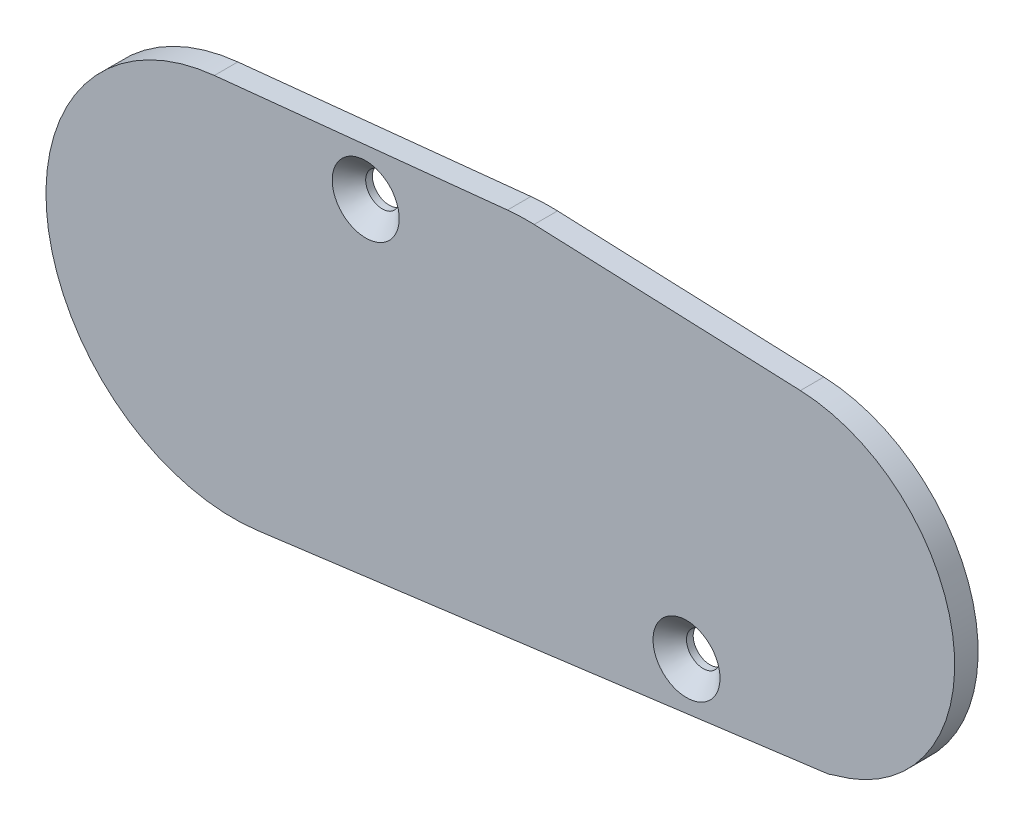
SolidWorks part; units mm, degrees
ref_plane "Front Plane" through (0, 0, 0) normal (0, 0, 1) x (1, 0, 0)
ref_plane "Top Plane" through (0, 0, 0) normal (0, 1, 0) x (1, 0, 0)
ref_plane "Right Plane" through (0, 0, 0) normal (1, 0, 0) x (0, 0, -1)
sketch "Sketch1" plane through (0, 0, 0) normal (0, 0, 1) x (1, 0, 0)
  line L0 (-43.969, -24.5) -> (-40.2721, -28.1969)
  line L2 (-40.2721, -28.1969) -> (-40.2721, -60)
  line L5 (63.3122, 76.6851) -> (41.4267, 78.9271)
  line L6 (39.439, 78.9888) -> (19.5552, 78.1913)
  line L7 (89.7279, -60) -> (89.7279, -34.5442)
  line L8 (77.7279, -22.5442) -> (52.2721, -22.5442)
  line L9 (40.2721, -34.5442) -> (40.2721, -60)
  line L10 (43.7868, -68.4853) -> (56.5147, -81.2132)
  line L11 (73.4853, -81.2132) -> (86.2132, -68.4853)
  line L12 (89.7279, -60) -> (89.7279, -34.5442)
  line L13 (-70.4772, -24.5) -> (-82.469, -24.5)
  line L14 (-84.469, -26.5) -> (-84.469, -49.0641)
  line L15 (-86.2132, -68.4853) -> (-73.4853, -81.2132)
  line L16 (-56.5147, -81.2132) -> (-43.7868, -68.4853)
  line L17 (-40.2721, -60) -> (-40.2721, -50)
  line L18 (-40.2721, -50) -> (-42.2721, -50)
  line L19 (-42.2721, -50) -> (-42.2721, -60)
  line L20 (-45.201, -67.0711) -> (-57.9289, -79.799)
  line L21 (-72.0711, -79.799) -> (-84.799, -67.0711)
  line L22 (-82.469, -51.1953) -> (-82.469, -26.5)
  line L23 (-82.469, -26.5) -> (-43.969, -26.5)
  line L24 (-43.969, -26.5) -> (-43.969, -24.5)
  line L25 (-43.969, -24.5) -> (-59.5228, -24.5)
  line L26 (-70.4772, -24.5) -> (-82.469, -24.5)
  line L27 (-84.469, -26.5) -> (-84.469, -49.0641)
  line L28 (-86.2132, -68.4853) -> (-73.4853, -81.2132)
  line L29 (-56.5147, -81.2132) -> (-43.7868, -68.4853)
  line L38 (-43.969, -24.5) -> (-59.5228, -24.5)
  line L39 (77.7279, -22.5442) -> (52.2721, -22.5442)
  line L40 (40.2721, -34.5442) -> (40.2721, -60)
  line L41 (43.7868, -68.4853) -> (56.5147, -81.2132)
  line L42 (73.4853, -81.2132) -> (86.2132, -68.4853)
  line L43 (17.3834, 54.4454) -> (60.0743, 48.8756)
  line L44 (63.3122, 76.6851) -> (41.4267, 78.9271)
  line L45 (39.439, 78.9888) -> (19.5552, 78.1913)
  line L46 (17.3834, 54.4454) -> (60.0743, 48.8756)
  line L47 (-41.4267, 78.9271) -> (-63.3122, 76.6851)
  line L48 (-60.0743, 48.8756) -> (-17.3834, 54.4454)
  line L49 (-19.5552, 78.1913) -> (-39.439, 78.9888)
  line L50 (-41.4267, 78.9271) -> (-63.3122, 76.6851)
  line L51 (-60.0743, 48.8756) -> (-17.3834, 54.4454)
  line L52 (-19.5552, 78.1913) -> (-39.439, 78.9888)
  circle A0 centre (-52.0128, 74.3243) radius 1.5 construction
  circle A1 centre (-52.0128, 74.3243) radius 1.5
  circle A2 centre (-28.0593, 56.5822) radius 1.5 construction
  circle A3 centre (-28.0593, 56.5822) radius 1.5
  arc A4 (60.0743, 48.8756) -> (63.3122, 76.6851) centre (61.8855, 62.758) ccw
  arc A5 (86.2132, -68.4853) -> (89.7279, -60) centre (77.7279, -60) ccw
  arc A6 (89.7279, -34.5442) -> (77.7279, -22.5442) centre (77.7279, -34.5442) ccw
  arc A7 (52.2721, -22.5442) -> (40.2721, -34.5442) centre (52.2721, -34.5442) ccw
  arc A8 (40.2721, -60) -> (43.7868, -68.4853) centre (52.2721, -60) ccw
  arc A9 (56.5147, -81.2132) -> (73.4853, -81.2132) centre (65, -72.7279) ccw
  arc A10 (86.2132, -68.4853) -> (89.7279, -60) centre (77.7279, -60) ccw
  arc A11 (-82.469, -24.5) -> (-84.469, -26.5) centre (-82.469, -26.5) ccw
  arc A12 (-85.2203, -50.6264) -> (-84.469, -49.0641) centre (-86.469, -49.0641) ccw
  arc A13 (-85.2203, -50.6264) -> (-86.2132, -68.4853) centre (-77.7279, -60) ccw
  arc A14 (-73.4853, -81.2132) -> (-56.5147, -81.2132) centre (-65, -72.7279) ccw
  arc A15 (-43.7868, -68.4853) -> (-40.2721, -60) centre (-52.2721, -60) ccw
  arc A16 (-45.201, -67.0711) -> (-42.2721, -60) centre (-52.2721, -60) ccw
  arc A17 (-72.0711, -79.799) -> (-57.9289, -79.799) centre (-65, -72.7279) ccw
  arc A18 (-82.469, -51.1953) -> (-84.799, -67.0711) centre (-77.7279, -60) ccw
  arc A19 (-61.5145, -22.6818) -> (-59.5228, -24.5) centre (-59.5228, -22.5) ccw
  arc A20 (-61.5145, -22.6818) -> (-68.4855, -22.6818) centre (-65, -23) ccw
  arc A21 (-70.4772, -24.5) -> (-68.4855, -22.6818) centre (-70.4772, -22.5) ccw
  arc A22 (-82.469, -24.5) -> (-84.469, -26.5) centre (-82.469, -26.5) ccw
  arc A23 (-85.2203, -50.6264) -> (-84.469, -49.0641) centre (-86.469, -49.0641) ccw
  arc A24 (-85.2203, -50.6264) -> (-86.2132, -68.4853) centre (-77.7279, -60) ccw
  arc A25 (-73.4853, -81.2132) -> (-56.5147, -81.2132) centre (-65, -72.7279) ccw
  arc A26 (-43.7868, -68.4853) -> (-40.2721, -60) centre (-52.2721, -60) ccw
  arc A30 (-61.5145, -22.6818) -> (-59.5228, -24.5) centre (-59.5228, -22.5) ccw
  arc A31 (-61.5145, -22.6818) -> (-68.4855, -22.6818) centre (-65, -23) ccw
  arc A32 (-70.4772, -24.5) -> (-68.4855, -22.6818) centre (-70.4772, -22.5) ccw
  arc A33 (89.7279, -34.5442) -> (77.7279, -22.5442) centre (77.7279, -34.5442) ccw
  arc A34 (52.2721, -22.5442) -> (40.2721, -34.5442) centre (52.2721, -34.5442) ccw
  arc A35 (40.2721, -60) -> (43.7868, -68.4853) centre (52.2721, -60) ccw
  arc A36 (56.5147, -81.2132) -> (73.4853, -81.2132) centre (65, -72.7279) ccw
  arc A37 (41.4267, 78.9271) -> (39.439, 78.9888) centre (40, 65) ccw
  arc A38 (19.5552, 78.1913) -> (16.9911, 54.5937) centre (20.0361, 66.201) ccw
  arc A39 (17.3834, 54.4454) -> (16.9911, 54.5937) centre (16.4837, 52.6592) ccw
  arc A40 (60.0743, 48.8756) -> (63.3122, 76.6851) centre (61.8855, 62.758) ccw
  arc A41 (41.4267, 78.9271) -> (39.439, 78.9888) centre (40, 65) ccw
  arc A42 (19.5552, 78.1913) -> (16.9911, 54.5937) centre (20.0361, 66.201) ccw
  arc A43 (17.3834, 54.4454) -> (16.9911, 54.5937) centre (16.4837, 52.6592) ccw
  arc A44 (-39.439, 78.9888) -> (-41.4267, 78.9271) centre (-40, 65) ccw
  arc A45 (-63.3122, 76.6851) -> (-60.0743, 48.8756) centre (-61.8855, 62.758) ccw
  arc A46 (-16.9911, 54.5937) -> (-17.3834, 54.4454) centre (-16.4837, 52.6592) ccw
  arc A47 (-16.9911, 54.5937) -> (-19.5552, 78.1913) centre (-20.0361, 66.201) ccw
  arc A48 (-39.439, 78.9888) -> (-41.4267, 78.9271) centre (-40, 65) ccw
  arc A49 (-63.3122, 76.6851) -> (-60.0743, 48.8756) centre (-61.8855, 62.758) ccw
  arc A50 (-16.9911, 54.5937) -> (-17.3834, 54.4454) centre (-16.4837, 52.6592) ccw
  arc A51 (-16.9911, 54.5937) -> (-19.5552, 78.1913) centre (-20.0361, 66.201) ccw
  circle A52 centre (52.0128, 74.3243) radius 1.5 construction
  circle A53 centre (52.0128, 74.3243) radius 1.5
  circle A54 centre (28.0593, 56.5822) radius 1.5 construction
  circle A55 centre (28.0593, 56.5822) radius 1.5
  circle A56 centre (65, -26.0442) radius 1.5 construction
  circle A57 centre (65, -26.0442) radius 1.5
  circle A58 centre (65, -60) radius 1.5 construction
  circle A59 centre (65, -60) radius 1.5
  circle A60 centre (-65, -23) radius 1.5 construction
  circle A61 centre (-65, -23) radius 1.5
  circle A62 centre (-65, -60) radius 1.5 construction
  circle A63 centre (-65, -60) radius 1.5
  circle A64 centre (-65, -60) radius 1.25
  circle A65 centre (-65, -23) radius 1.25
  circle A66 centre (65, -60) radius 1.25
  circle A67 centre (65, -26.0442) radius 1.25
  circle A68 centre (52.0128, 74.3243) radius 1.25
  circle A69 centre (28.0593, 56.5822) radius 1.25
  circle A70 centre (-28.0593, 56.5822) radius 1.25
  circle A71 centre (-52.0128, 74.3243) radius 1.25
  dimension "D6" = 2.5
  dimension "D2" = 135
  dimension "D1" = 0
  dimension "D3" = 0
  dimension "D4" = 0
  dimension "D5" = 0
extrude "Boss-Extrude1" add sketch "Sketch1" along normal blind 1.75 contours L2 A26 L29 A25 L28 A24 A23 L27 A22 L26 A32 A31 A30 L38 L0 | A65 | A64 | L42 A10 L12 A33 L39 A34 L40 A35 L41 A36 | A66 | A67 | A40 L44 A41 L45 A42 A43 L46 | A68 | A69 | L51 A50 A51 L52 A48 L50 A49 | A70 | A71
hole_wizard "CSK for M2.5 Flat Head Machine Screw1" positions "Sketch2" profile "Sketch3" countersink size "M2.5" standard "ANSI Metric" end condition through all
sketch "Sketch2" plane through (0, 0, 1.75) normal (0, 0, 1) x (1, 0, 0)
  point P0 (-65, -23)
  point P3 (-65, -60)
  point P6 (-52.0128, 74.3243)
  point P9 (-28.0593, 56.5822)
  point P12 (52.0128, 74.3243)
  point P15 (28.0593, 56.5822)
  point P18 (65, -26.0442)
  point P21 (65, -60)
sketch "Sketch3" plane through (-65, -23, 1.75) normal (1, 0, 0) x (0, -1, 0)
  line L0 (0, 0) -> (0, 1.75)
  line L1 (0, 1.75) -> (1.25, 1.75)
  line L2 (1.25, 1.75) -> (1.25, 1.25)
  line L3 (1.25, 1.25) -> (2.5, 0)
  line L5 (2.5, 0) -> (0, 0)
  line L6 (-1.25, 1.25) -> (-2.5, 0) construction
  line L11 (0, -6.35) -> (0, 107.95) construction
  dimension "Thru Hole Dia." = 2.5
  dimension "Thru Hole Depth" = 1.75
  dimension "Near C'Sink Dia." = 5
  dimension "Near C'Sink Angle" = 90
fillet "Fillet1" radius 2 2 edges at (-40.2721, -28.1969, 0.875) (-43.969, -24.5, 0.875)
sketch "Sketch4" [suppressed] plane through (0, 0, 1.75) normal (0, 0, 1) x (1, 0, 0)
  line L0 (-60.0743, 48.8756) -> (-17.3834, 54.4454) construction
  line L1 (-19.5552, 78.1913) -> (-39.439, 78.9888) construction
  line L2 (-41.4267, 78.9271) -> (-63.3122, 76.6851) construction
  line L3 (17.3834, 54.4454) -> (60.0743, 48.8756) construction
  line L4 (63.3122, 76.6851) -> (41.4267, 78.9271) construction
  line L5 (39.439, 78.9888) -> (19.5552, 78.1913) construction
  line L6 (73.4853, -81.2132) -> (86.2132, -68.4853) construction
  line L7 (89.7279, -60) -> (89.7279, -34.5442) construction
  line L8 (77.7279, -22.5442) -> (52.2721, -22.5442) construction
  line L9 (40.2721, -34.5442) -> (40.2721, -60) construction
  line L10 (43.7868, -68.4853) -> (56.5147, -81.2132) construction
  line L11 (-60.0743, 48.8756) -> (-17.3834, 54.4454)
  line L12 (-19.5552, 78.1913) -> (-39.439, 78.9888)
  line L13 (-41.4267, 78.9271) -> (-63.3122, 76.6851)
  line L14 (17.3834, 54.4454) -> (60.0743, 48.8756)
  line L15 (63.3122, 76.6851) -> (41.4267, 78.9271)
  line L16 (39.439, 78.9888) -> (19.5552, 78.1913)
  line L17 (73.4853, -81.2132) -> (86.2132, -68.4853)
  line L18 (89.7279, -60) -> (89.7279, -34.5442)
  line L19 (77.7279, -22.5442) -> (52.2721, -22.5442)
  line L20 (40.2721, -34.5442) -> (40.2721, -60)
  line L21 (43.7868, -68.4853) -> (56.5147, -81.2132)
  arc A0 (-63.3122, 76.6851) -> (-60.0743, 48.8756) centre (-61.8855, 62.758) ccw construction
  arc A1 (-16.9911, 54.5937) -> (-17.3834, 54.4454) centre (-16.4837, 52.6592) ccw construction
  arc A2 (-16.9911, 54.5937) -> (-19.5552, 78.1913) centre (-20.0361, 66.201) ccw construction
  arc A3 (-39.439, 78.9888) -> (-41.4267, 78.9271) centre (-40, 65) ccw construction
  arc A4 (60.0743, 48.8756) -> (63.3122, 76.6851) centre (61.8855, 62.758) ccw construction
  arc A5 (41.4267, 78.9271) -> (39.439, 78.9888) centre (40, 65) ccw construction
  arc A6 (19.5552, 78.1913) -> (16.9911, 54.5937) centre (20.0361, 66.201) ccw construction
  arc A7 (17.3834, 54.4454) -> (16.9911, 54.5937) centre (16.4837, 52.6592) ccw construction
  arc A8 (56.5147, -81.2132) -> (73.4853, -81.2132) centre (65, -72.7279) ccw construction
  arc A9 (86.2132, -68.4853) -> (89.7279, -60) centre (77.7279, -60) ccw construction
  arc A10 (89.7279, -34.5442) -> (77.7279, -22.5442) centre (77.7279, -34.5442) ccw construction
  arc A11 (52.2721, -22.5442) -> (40.2721, -34.5442) centre (52.2721, -34.5442) ccw construction
  arc A12 (40.2721, -60) -> (43.7868, -68.4853) centre (52.2721, -60) ccw construction
  arc A13 (-63.3122, 76.6851) -> (-60.0743, 48.8756) centre (-61.8855, 62.758) ccw
  arc A14 (-16.9911, 54.5937) -> (-17.3834, 54.4454) centre (-16.4837, 52.6592) ccw
  arc A15 (-16.9911, 54.5937) -> (-19.5552, 78.1913) centre (-20.0361, 66.201) ccw
  arc A16 (-39.439, 78.9888) -> (-41.4267, 78.9271) centre (-40, 65) ccw
  arc A17 (60.0743, 48.8756) -> (63.3122, 76.6851) centre (61.8855, 62.758) ccw
  arc A18 (41.4267, 78.9271) -> (39.439, 78.9888) centre (40, 65) ccw
  arc A19 (19.5552, 78.1913) -> (16.9911, 54.5937) centre (20.0361, 66.201) ccw
  arc A20 (17.3834, 54.4454) -> (16.9911, 54.5937) centre (16.4837, 52.6592) ccw
  arc A21 (56.5147, -81.2132) -> (73.4853, -81.2132) centre (65, -72.7279) ccw
  arc A22 (86.2132, -68.4853) -> (89.7279, -60) centre (77.7279, -60) ccw
  arc A23 (89.7279, -34.5442) -> (77.7279, -22.5442) centre (77.7279, -34.5442) ccw
  arc A24 (52.2721, -22.5442) -> (40.2721, -34.5442) centre (52.2721, -34.5442) ccw
  arc A25 (40.2721, -60) -> (43.7868, -68.4853) centre (52.2721, -60) ccw
extrude "Cut-Extrude1" [suppressed] cut sketch "Sketch4" against normal up to next
sketch "Sketch5" [suppressed] plane through (0, 0, 1.75) normal (0, 0, 1) x (1, 0, 0)
  line L0 (17.3834, 54.4454) -> (60.0743, 48.8756) construction
  line L1 (63.3122, 76.6851) -> (41.4267, 78.9271) construction
  line L2 (39.439, 78.9888) -> (19.5552, 78.1913) construction
  line L3 (-60.0743, 48.8756) -> (-17.3834, 54.4454) construction
  line L4 (-19.5552, 78.1913) -> (-39.439, 78.9888) construction
  line L5 (-41.4267, 78.9271) -> (-63.3122, 76.6851) construction
  line L6 (-40.2721, -60) -> (-40.2721, -29.0253) construction
  line L7 (-40.8579, -27.6111) -> (-43.3832, -25.0858) construction
  line L8 (-44.7974, -24.5) -> (-59.5228, -24.5) construction
  line L9 (-70.4772, -24.5) -> (-82.469, -24.5) construction
  line L10 (-84.469, -26.5) -> (-84.469, -49.0641) construction
  line L11 (-86.2132, -68.4853) -> (-73.4853, -81.2132) construction
  line L12 (-56.5147, -81.2132) -> (-43.7868, -68.4853) construction
  line L13 (17.3834, 54.4454) -> (60.0743, 48.8756)
  line L14 (63.3122, 76.6851) -> (41.4267, 78.9271)
  line L15 (39.439, 78.9888) -> (19.5552, 78.1913)
  line L16 (-60.0743, 48.8756) -> (-17.3834, 54.4454)
  line L17 (-19.5552, 78.1913) -> (-39.439, 78.9888)
  line L18 (-41.4267, 78.9271) -> (-63.3122, 76.6851)
  line L19 (-40.2721, -60) -> (-40.2721, -29.0253)
  line L20 (-40.8579, -27.6111) -> (-43.3832, -25.0858)
  line L21 (-44.7974, -24.5) -> (-59.5228, -24.5)
  line L22 (-70.4772, -24.5) -> (-82.469, -24.5)
  line L23 (-84.469, -26.5) -> (-84.469, -49.0641)
  line L24 (-86.2132, -68.4853) -> (-73.4853, -81.2132)
  line L25 (-56.5147, -81.2132) -> (-43.7868, -68.4853)
  arc A0 (60.0743, 48.8756) -> (63.3122, 76.6851) centre (61.8855, 62.758) ccw construction
  arc A1 (41.4267, 78.9271) -> (39.439, 78.9888) centre (40, 65) ccw construction
  arc A2 (19.5552, 78.1913) -> (16.9911, 54.5937) centre (20.0361, 66.201) ccw construction
  arc A3 (17.3834, 54.4454) -> (16.9911, 54.5937) centre (16.4837, 52.6592) ccw construction
  arc A4 (-63.3122, 76.6851) -> (-60.0743, 48.8756) centre (-61.8855, 62.758) ccw construction
  arc A5 (-16.9911, 54.5937) -> (-17.3834, 54.4454) centre (-16.4837, 52.6592) ccw construction
  arc A6 (-16.9911, 54.5937) -> (-19.5552, 78.1913) centre (-20.0361, 66.201) ccw construction
  arc A7 (-39.439, 78.9888) -> (-41.4267, 78.9271) centre (-40, 65) ccw construction
  arc A8 (-40.2721, -29.0253) -> (-40.8579, -27.6111) centre (-42.2721, -29.0253) ccw construction
  arc A9 (-43.3832, -25.0858) -> (-44.7974, -24.5) centre (-44.7974, -26.5) ccw construction
  arc A10 (-61.5145, -22.6818) -> (-59.5228, -24.5) centre (-59.5228, -22.5) ccw construction
  arc A11 (-61.5145, -22.6818) -> (-68.4855, -22.6818) centre (-65, -23) ccw construction
  arc A12 (-70.4772, -24.5) -> (-68.4855, -22.6818) centre (-70.4772, -22.5) ccw construction
  arc A13 (-82.469, -24.5) -> (-84.469, -26.5) centre (-82.469, -26.5) ccw construction
  arc A14 (-85.2203, -50.6264) -> (-84.469, -49.0641) centre (-86.469, -49.0641) ccw construction
  arc A15 (-85.2203, -50.6264) -> (-86.2132, -68.4853) centre (-77.7279, -60) ccw construction
  arc A16 (-73.4853, -81.2132) -> (-56.5147, -81.2132) centre (-65, -72.7279) ccw construction
  arc A17 (-43.7868, -68.4853) -> (-40.2721, -60) centre (-52.2721, -60) ccw construction
  arc A18 (60.0743, 48.8756) -> (63.3122, 76.6851) centre (61.8855, 62.758) ccw
  arc A19 (41.4267, 78.9271) -> (39.439, 78.9888) centre (40, 65) ccw
  arc A20 (19.5552, 78.1913) -> (16.9911, 54.5937) centre (20.0361, 66.201) ccw
  arc A21 (17.3834, 54.4454) -> (16.9911, 54.5937) centre (16.4837, 52.6592) ccw
  arc A22 (-63.3122, 76.6851) -> (-60.0743, 48.8756) centre (-61.8855, 62.758) ccw
  arc A23 (-16.9911, 54.5937) -> (-17.3834, 54.4454) centre (-16.4837, 52.6592) ccw
  arc A24 (-16.9911, 54.5937) -> (-19.5552, 78.1913) centre (-20.0361, 66.201) ccw
  arc A25 (-39.439, 78.9888) -> (-41.4267, 78.9271) centre (-40, 65) ccw
  arc A26 (-40.2721, -29.0253) -> (-40.8579, -27.6111) centre (-42.2721, -29.0253) ccw
  arc A27 (-43.3832, -25.0858) -> (-44.7974, -24.5) centre (-44.7974, -26.5) ccw
  arc A28 (-61.5145, -22.6818) -> (-59.5228, -24.5) centre (-59.5228, -22.5) ccw
  arc A29 (-61.5145, -22.6818) -> (-68.4855, -22.6818) centre (-65, -23) ccw
  arc A30 (-70.4772, -24.5) -> (-68.4855, -22.6818) centre (-70.4772, -22.5) ccw
  arc A31 (-82.469, -24.5) -> (-84.469, -26.5) centre (-82.469, -26.5) ccw
  arc A32 (-85.2203, -50.6264) -> (-84.469, -49.0641) centre (-86.469, -49.0641) ccw
  arc A33 (-85.2203, -50.6264) -> (-86.2132, -68.4853) centre (-77.7279, -60) ccw
  arc A34 (-73.4853, -81.2132) -> (-56.5147, -81.2132) centre (-65, -72.7279) ccw
  arc A35 (-43.7868, -68.4853) -> (-40.2721, -60) centre (-52.2721, -60) ccw
extrude "Cut-Extrude2" [suppressed] cut sketch "Sketch5" against normal up to next
sketch "Sketch6" [suppressed] plane through (0, 0, 1.75) normal (0, 0, 1) x (1, 0, 0)
  line L0 (73.4853, -81.2132) -> (86.2132, -68.4853) construction
  line L1 (89.7279, -60) -> (89.7279, -34.5442) construction
  line L2 (77.7279, -22.5442) -> (52.2721, -22.5442) construction
  line L3 (40.2721, -34.5442) -> (40.2721, -60) construction
  line L4 (43.7868, -68.4853) -> (56.5147, -81.2132) construction
  line L5 (-60.0743, 48.8756) -> (-17.3834, 54.4454) construction
  line L6 (-19.5552, 78.1913) -> (-39.439, 78.9888) construction
  line L7 (-41.4267, 78.9271) -> (-63.3122, 76.6851) construction
  line L8 (-40.2721, -60) -> (-40.2721, -29.0253) construction
  line L9 (-40.8579, -27.6111) -> (-43.3832, -25.0858) construction
  line L10 (-44.7974, -24.5) -> (-59.5228, -24.5) construction
  line L11 (-70.4772, -24.5) -> (-82.469, -24.5) construction
  line L12 (-84.469, -26.5) -> (-84.469, -49.0641) construction
  line L13 (-86.2132, -68.4853) -> (-73.4853, -81.2132) construction
  line L14 (-56.5147, -81.2132) -> (-43.7868, -68.4853) construction
  line L15 (73.4853, -81.2132) -> (86.2132, -68.4853)
  line L16 (89.7279, -60) -> (89.7279, -34.5442)
  line L17 (77.7279, -22.5442) -> (52.2721, -22.5442)
  line L18 (40.2721, -34.5442) -> (40.2721, -60)
  line L19 (43.7868, -68.4853) -> (56.5147, -81.2132)
  line L20 (-60.0743, 48.8756) -> (-17.3834, 54.4454)
  line L21 (-19.5552, 78.1913) -> (-39.439, 78.9888)
  line L22 (-41.4267, 78.9271) -> (-63.3122, 76.6851)
  line L23 (-40.2721, -60) -> (-40.2721, -29.0253)
  line L24 (-40.8579, -27.6111) -> (-43.3832, -25.0858)
  line L25 (-44.7974, -24.5) -> (-59.5228, -24.5)
  line L26 (-70.4772, -24.5) -> (-82.469, -24.5)
  line L27 (-84.469, -26.5) -> (-84.469, -49.0641)
  line L28 (-86.2132, -68.4853) -> (-73.4853, -81.2132)
  line L29 (-56.5147, -81.2132) -> (-43.7868, -68.4853)
  arc A0 (56.5147, -81.2132) -> (73.4853, -81.2132) centre (65, -72.7279) ccw construction
  arc A1 (86.2132, -68.4853) -> (89.7279, -60) centre (77.7279, -60) ccw construction
  arc A2 (89.7279, -34.5442) -> (77.7279, -22.5442) centre (77.7279, -34.5442) ccw construction
  arc A3 (52.2721, -22.5442) -> (40.2721, -34.5442) centre (52.2721, -34.5442) ccw construction
  arc A4 (40.2721, -60) -> (43.7868, -68.4853) centre (52.2721, -60) ccw construction
  arc A5 (-63.3122, 76.6851) -> (-60.0743, 48.8756) centre (-61.8855, 62.758) ccw construction
  arc A6 (-16.9911, 54.5937) -> (-17.3834, 54.4454) centre (-16.4837, 52.6592) ccw construction
  arc A7 (-16.9911, 54.5937) -> (-19.5552, 78.1913) centre (-20.0361, 66.201) ccw construction
  arc A8 (-39.439, 78.9888) -> (-41.4267, 78.9271) centre (-40, 65) ccw construction
  arc A9 (-40.2721, -29.0253) -> (-40.8579, -27.6111) centre (-42.2721, -29.0253) ccw construction
  arc A10 (-43.3832, -25.0858) -> (-44.7974, -24.5) centre (-44.7974, -26.5) ccw construction
  arc A11 (-61.5145, -22.6818) -> (-59.5228, -24.5) centre (-59.5228, -22.5) ccw construction
  arc A12 (-61.5145, -22.6818) -> (-68.4855, -22.6818) centre (-65, -23) ccw construction
  arc A13 (-70.4772, -24.5) -> (-68.4855, -22.6818) centre (-70.4772, -22.5) ccw construction
  arc A14 (-82.469, -24.5) -> (-84.469, -26.5) centre (-82.469, -26.5) ccw construction
  arc A15 (-85.2203, -50.6264) -> (-84.469, -49.0641) centre (-86.469, -49.0641) ccw construction
  arc A16 (-85.2203, -50.6264) -> (-86.2132, -68.4853) centre (-77.7279, -60) ccw construction
  arc A17 (-73.4853, -81.2132) -> (-56.5147, -81.2132) centre (-65, -72.7279) ccw construction
  arc A18 (-43.7868, -68.4853) -> (-40.2721, -60) centre (-52.2721, -60) ccw construction
  arc A19 (56.5147, -81.2132) -> (73.4853, -81.2132) centre (65, -72.7279) ccw
  arc A20 (86.2132, -68.4853) -> (89.7279, -60) centre (77.7279, -60) ccw
  arc A21 (89.7279, -34.5442) -> (77.7279, -22.5442) centre (77.7279, -34.5442) ccw
  arc A22 (52.2721, -22.5442) -> (40.2721, -34.5442) centre (52.2721, -34.5442) ccw
  arc A23 (40.2721, -60) -> (43.7868, -68.4853) centre (52.2721, -60) ccw
  arc A24 (-63.3122, 76.6851) -> (-60.0743, 48.8756) centre (-61.8855, 62.758) ccw
  arc A25 (-16.9911, 54.5937) -> (-17.3834, 54.4454) centre (-16.4837, 52.6592) ccw
  arc A26 (-16.9911, 54.5937) -> (-19.5552, 78.1913) centre (-20.0361, 66.201) ccw
  arc A27 (-39.439, 78.9888) -> (-41.4267, 78.9271) centre (-40, 65) ccw
  arc A28 (-40.2721, -29.0253) -> (-40.8579, -27.6111) centre (-42.2721, -29.0253) ccw
  arc A29 (-43.3832, -25.0858) -> (-44.7974, -24.5) centre (-44.7974, -26.5) ccw
  arc A30 (-61.5145, -22.6818) -> (-59.5228, -24.5) centre (-59.5228, -22.5) ccw
  arc A31 (-61.5145, -22.6818) -> (-68.4855, -22.6818) centre (-65, -23) ccw
  arc A32 (-70.4772, -24.5) -> (-68.4855, -22.6818) centre (-70.4772, -22.5) ccw
  arc A33 (-82.469, -24.5) -> (-84.469, -26.5) centre (-82.469, -26.5) ccw
  arc A34 (-85.2203, -50.6264) -> (-84.469, -49.0641) centre (-86.469, -49.0641) ccw
  arc A35 (-85.2203, -50.6264) -> (-86.2132, -68.4853) centre (-77.7279, -60) ccw
  arc A36 (-73.4853, -81.2132) -> (-56.5147, -81.2132) centre (-65, -72.7279) ccw
  arc A37 (-43.7868, -68.4853) -> (-40.2721, -60) centre (-52.2721, -60) ccw
extrude "Cut-Extrude3" [suppressed] cut sketch "Sketch6" against normal up to next
sketch "Sketch7" plane through (0, 0, 1.75) normal (0, 0, 1) x (1, 0, 0)
  line L0 (-40.2721, -60) -> (-40.2721, -29.0253) construction
  line L1 (-40.8579, -27.6111) -> (-43.3832, -25.0858) construction
  line L2 (-44.7974, -24.5) -> (-59.5228, -24.5) construction
  line L3 (-70.4772, -24.5) -> (-82.469, -24.5) construction
  line L4 (-84.469, -26.5) -> (-84.469, -49.0641) construction
  line L5 (-86.2132, -68.4853) -> (-73.4853, -81.2132) construction
  line L6 (-56.5147, -81.2132) -> (-43.7868, -68.4853) construction
  line L7 (73.4853, -81.2132) -> (86.2132, -68.4853) construction
  line L8 (89.7279, -60) -> (89.7279, -34.5442) construction
  line L9 (77.7279, -22.5442) -> (52.2721, -22.5442) construction
  line L10 (40.2721, -34.5442) -> (40.2721, -60) construction
  line L11 (43.7868, -68.4853) -> (56.5147, -81.2132) construction
  line L12 (17.3834, 54.4454) -> (60.0743, 48.8756) construction
  line L13 (63.3122, 76.6851) -> (41.4267, 78.9271) construction
  line L14 (39.439, 78.9888) -> (19.5552, 78.1913) construction
  line L15 (-40.2721, -60) -> (-40.2721, -29.0253)
  line L16 (-40.8579, -27.6111) -> (-43.3832, -25.0858)
  line L17 (-44.7974, -24.5) -> (-59.5228, -24.5)
  line L18 (-70.4772, -24.5) -> (-82.469, -24.5)
  line L19 (-84.469, -26.5) -> (-84.469, -49.0641)
  line L20 (-86.2132, -68.4853) -> (-73.4853, -81.2132)
  line L21 (-56.5147, -81.2132) -> (-43.7868, -68.4853)
  line L22 (73.4853, -81.2132) -> (86.2132, -68.4853)
  line L23 (89.7279, -60) -> (89.7279, -34.5442)
  line L24 (77.7279, -22.5442) -> (52.2721, -22.5442)
  line L25 (40.2721, -34.5442) -> (40.2721, -60)
  line L26 (43.7868, -68.4853) -> (56.5147, -81.2132)
  line L27 (17.3834, 54.4454) -> (60.0743, 48.8756)
  line L28 (63.3122, 76.6851) -> (41.4267, 78.9271)
  line L29 (39.439, 78.9888) -> (19.5552, 78.1913)
  arc A0 (-40.2721, -29.0253) -> (-40.8579, -27.6111) centre (-42.2721, -29.0253) ccw construction
  arc A1 (-43.3832, -25.0858) -> (-44.7974, -24.5) centre (-44.7974, -26.5) ccw construction
  arc A2 (-61.5145, -22.6818) -> (-59.5228, -24.5) centre (-59.5228, -22.5) ccw construction
  arc A3 (-61.5145, -22.6818) -> (-68.4855, -22.6818) centre (-65, -23) ccw construction
  arc A4 (-70.4772, -24.5) -> (-68.4855, -22.6818) centre (-70.4772, -22.5) ccw construction
  arc A5 (-82.469, -24.5) -> (-84.469, -26.5) centre (-82.469, -26.5) ccw construction
  arc A6 (-85.2203, -50.6264) -> (-84.469, -49.0641) centre (-86.469, -49.0641) ccw construction
  arc A7 (-85.2203, -50.6264) -> (-86.2132, -68.4853) centre (-77.7279, -60) ccw construction
  arc A8 (-73.4853, -81.2132) -> (-56.5147, -81.2132) centre (-65, -72.7279) ccw construction
  arc A9 (-43.7868, -68.4853) -> (-40.2721, -60) centre (-52.2721, -60) ccw construction
  arc A10 (56.5147, -81.2132) -> (73.4853, -81.2132) centre (65, -72.7279) ccw construction
  arc A11 (86.2132, -68.4853) -> (89.7279, -60) centre (77.7279, -60) ccw construction
  arc A12 (89.7279, -34.5442) -> (77.7279, -22.5442) centre (77.7279, -34.5442) ccw construction
  arc A13 (52.2721, -22.5442) -> (40.2721, -34.5442) centre (52.2721, -34.5442) ccw construction
  arc A14 (40.2721, -60) -> (43.7868, -68.4853) centre (52.2721, -60) ccw construction
  arc A15 (60.0743, 48.8756) -> (63.3122, 76.6851) centre (61.8855, 62.758) ccw construction
  arc A16 (41.4267, 78.9271) -> (39.439, 78.9888) centre (40, 65) ccw construction
  arc A17 (19.5552, 78.1913) -> (16.9911, 54.5937) centre (20.0361, 66.201) ccw construction
  arc A18 (17.3834, 54.4454) -> (16.9911, 54.5937) centre (16.4837, 52.6592) ccw construction
  arc A19 (-40.2721, -29.0253) -> (-40.8579, -27.6111) centre (-42.2721, -29.0253) ccw
  arc A20 (-43.3832, -25.0858) -> (-44.7974, -24.5) centre (-44.7974, -26.5) ccw
  arc A21 (-61.5145, -22.6818) -> (-59.5228, -24.5) centre (-59.5228, -22.5) ccw
  arc A22 (-61.5145, -22.6818) -> (-68.4855, -22.6818) centre (-65, -23) ccw
  arc A23 (-70.4772, -24.5) -> (-68.4855, -22.6818) centre (-70.4772, -22.5) ccw
  arc A24 (-82.469, -24.5) -> (-84.469, -26.5) centre (-82.469, -26.5) ccw
  arc A25 (-85.2203, -50.6264) -> (-84.469, -49.0641) centre (-86.469, -49.0641) ccw
  arc A26 (-85.2203, -50.6264) -> (-86.2132, -68.4853) centre (-77.7279, -60) ccw
  arc A27 (-73.4853, -81.2132) -> (-56.5147, -81.2132) centre (-65, -72.7279) ccw
  arc A28 (-43.7868, -68.4853) -> (-40.2721, -60) centre (-52.2721, -60) ccw
  arc A29 (56.5147, -81.2132) -> (73.4853, -81.2132) centre (65, -72.7279) ccw
  arc A30 (86.2132, -68.4853) -> (89.7279, -60) centre (77.7279, -60) ccw
  arc A31 (89.7279, -34.5442) -> (77.7279, -22.5442) centre (77.7279, -34.5442) ccw
  arc A32 (52.2721, -22.5442) -> (40.2721, -34.5442) centre (52.2721, -34.5442) ccw
  arc A33 (40.2721, -60) -> (43.7868, -68.4853) centre (52.2721, -60) ccw
  arc A34 (60.0743, 48.8756) -> (63.3122, 76.6851) centre (61.8855, 62.758) ccw
  arc A35 (41.4267, 78.9271) -> (39.439, 78.9888) centre (40, 65) ccw
  arc A36 (19.5552, 78.1913) -> (16.9911, 54.5937) centre (20.0361, 66.201) ccw
  arc A37 (17.3834, 54.4454) -> (16.9911, 54.5937) centre (16.4837, 52.6592) ccw
extrude "Cut-Extrude4" cut sketch "Sketch7" against normal up to next (1.75 mm away)
